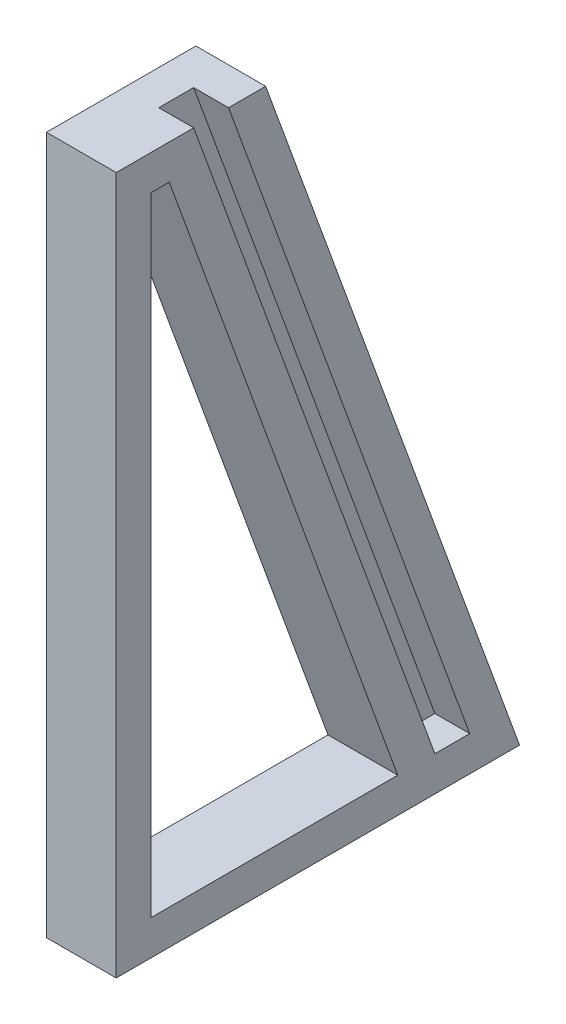
SolidWorks part; units mm, degrees
ref_plane "Front Plane" through (0, 0, 0) normal (0, 0, 1) x (1, 0, 0)
ref_plane "Top Plane" through (0, 0, 0) normal (0, 1, 0) x (1, 0, 0)
ref_plane "Right Plane" through (0, 0, 0) normal (1, 0, 0) x (0, 0, -1)
sketch "Sketch1" plane through (0, 0, 0) normal (1, 0, 0) x (0, 0, -1)
  line L1 (-50, 50) -> (50, 50)
  line L2 (-50, 50) -> (-50, -50)
  line L3 (-50, -50) -> (50, -50)
  line L4 (50, 50) -> (50, -50)
  line L5 (-50, 50) -> (50, -50) construction
  line L6 (-50, -50) -> (50, 50) construction
  point P0 (0, 0)
  dimension "D1" = 100
  dimension "D2" = 100
extrude "Boss-Extrude1" add sketch "Sketch1" along normal blind 10
sketch "Sketch2" plane through (0, 0, 0) normal (-1, 0, 0) x (0, 0, 1)
  line L0 (-50, -50) -> (-50, 50)
  line L1 (-50, 50) -> (50, 50)
  line L2 (50, 50) -> (50, -50)
  line L3 (50, -50) -> (-50, -50)
  line L4 (38.897, 50) -> (50, 50)
  line L5 (0, -50) -> (2.5, -50)
  line L6 (0, -50) -> (-2.5, -50)
  line L7 (36.397, 50) -> (38.897, 50)
  line L8 (36.397, 50) -> (33.897, 50)
  line L9 (33.897, 50) -> (-2.5, -50)
  line L10 (38.897, 50) -> (2.5, -50)
  line L11 (50, -50) -> (50, 50)
  line L12 (50, -50) -> (2.5, -50)
  line L13 (2.5, -50) -> (38.897, 50)
  line L14 (7.1985, -51.7101) -> (7.8209, -50)
  line L15 (45, 45) -> (45, -45)
  line L16 (45, -45) -> (9.6407, -45)
  line L17 (9.6407, -45) -> (42.3981, 45)
  line L18 (50, -45) -> (-45, -45) construction
  line L19 (7.1985, -51.7101) -> (43.5955, 48.2899) construction
  line L20 (45, 50) -> (45, -50) construction
  line L21 (42.3981, 45) -> (45, 45)
  line L22 (-45, 45) -> (50, 45) construction
  line L23 (-0.6801, -45) -> (4.3199, -45)
  line L24 (-45, -45) -> (-45, 45) construction
  line L25 (-50, 50) -> (33.897, 50)
  line L26 (-2.5, -50) -> (33.897, 50)
  line L27 (-50, 50) -> (-50, -50)
  line L28 (-2.5, -50) -> (-50, -50)
  line M16 (-50, 50) -> (-50, -50)
  line M17 (-50, -50) -> (50, -50)
  dimension "D1" = 5
  dimension "D2" = 2.5
  dimension "D3" = 2.5
  dimension "D4" = 70
extrude "Cut-Extrude1" cut sketch "Sketch2" against normal blind 10 contours L21 L17 L16 L15 region at (0, -12.9437, 33.1541)
sketch "Sketch3" plane through (0, -50, 0) normal (0, -1, 0) x (1, 0, 0)
  line L0 (10, 50) -> (10, -50)
sketch "Sketch4" plane through (0, -50, 0) normal (0, -1, 0) x (1, 0, 0)
  line L0 (10, 50) -> (10, -50)
  line L1 (10, -50) -> (0, -50)
  line L2 (0, -50) -> (0, 50)
  line L3 (0, 50) -> (10, 50)
  line L4 (0, 50) -> (0, 40)
  line L5 (0, 40) -> (10, 40)
  line L6 (10, 40) -> (10, 50)
  line L7 (10, -50) -> (10, -40)
  line L8 (10, -40) -> (0, -40)
  line L9 (0, -40) -> (0, -50)
  line L10 (10, 0) -> (0, 0)
  line L11 (10, 0) -> (10, 0.3209)
  line L12 (10, 0.3209) -> (0, 0.3209)
  line L13 (0, 0.3209) -> (0, 0)
  line L14 (0, 0.3209) -> (0, 10.3209)
  line L15 (0, 10.3209) -> (10, 10.3209)
  line L16 (10, 10.3209) -> (10, 0.3209)
  line L17 (10, 10.3209) -> (10, 5.3209)
  line L18 (10, 45) -> (5, 45)
  line L19 (5, 45) -> (5, 50)
  line L20 (8, 8.3209) -> (2, 8.3209)
  line L21 (8, 8.3209) -> (8, 2.3209)
  line L22 (8, 2.3209) -> (2, 2.3209)
  line L23 (2, 8.3209) -> (2, 2.3209)
  line L24 (8, 8.3209) -> (2, 2.3209) construction
  line L25 (8, 2.3209) -> (2, 8.3209) construction
  line L26 (8, -42) -> (2, -42)
  line L27 (8, 48) -> (2, 48)
  line L28 (8, 48) -> (8, 42)
  line L29 (8, 42) -> (2, 42)
  line L30 (2, 48) -> (2, 42)
  line L31 (8, 48) -> (2, 42) construction
  line L32 (8, 42) -> (2, 48) construction
  line L33 (2, -48) -> (2, -42)
  line L34 (8, -48) -> (2, -48)
  line L35 (8, -48) -> (8, -42)
  line L36 (5, 5.3209) -> (10, 5.3209)
  line L37 (5, 5.3209) -> (5, 0.3209)
  line L38 (5, -50) -> (5, -45)
  line L39 (5, -45) -> (10, -45)
  dimension "D1" = 6
  dimension "D2" = 6
  dimension "D3" = 6
  dimension "D4" = 6
extrude "Cut-Extrude3" cut sketch "Sketch4" against normal blind 4 contours L34 L35 L26 L33 | L20 L23 L22 L21 | L27 L30 L29 L28 L18 L19 | L28 L27 L19 L18 | L36 L37 L22 L21 | L39 L38 L34 L35 region at (4.5, -50, 44.5) region at (6.5, -50, 46.5) region at (4.5, -50, 5.8209) region at (6.5, -50, 3.8209) region at (4.5, -50, -44.5) region at (6.5, -50, -46.5)
sketch "Sketch6" plane through (10, 0, 0) normal (1, 0, 0) x (0, 0, -1)
  line L0 (-38.897, 50) -> (-33.897, 50)
  line L1 (-33.897, 50) -> (0.6801, -45)
  line L2 (0.6801, -45) -> (-4.3199, -45)
  line L3 (-4.3199, -45) -> (-38.897, 50)
extrude "Cut-Extrude5" cut sketch "Sketch2<4>" against normal blind 10 contours L9 L1 M16 M17 region at (0, 4.6167, -16.3106)
sketch "Sketch2<4>" plane through (0, 0, 0) normal (-1, 0, 0) x (0, 0, 1) same geometry as "Sketch2"
extrude "Cut-Extrude6" cut sketch "Sketch6" against normal blind 5
sketch "Sketch8" plane through (0, 0, 0) normal (-1, 0, 0) x (0, 0, 1)
  line L0 (33.897, 50) -> (-2.5, -50)
  line L1 (-2.5, -50) -> (-50, -50)
  line L2 (-50, -50) -> (-50, 50)
  line L3 (-50, 50) -> (33.897, 50)
  line L5 (26.7563, 45) -> (-6.001, -45)
  line L8 (26.7563, 45) -> (28.5761, 50)
  line L9 (-6.001, -45) -> (-7.8209, -50)
  line L11 (-45, 45) -> (26.7563, 45) construction
  line L12 (-6.001, -45) -> (-45, -45) construction
  line L13 (-45, -45) -> (-45, 45) construction
  line M15 (33.897, 50) -> (-2.5, -50)
  dimension "D2" = 180
  dimension "D3" = 180
  dimension "D1" = 5
extrude "Boss-Extrude2" add sketch "Sketch8" against normal blind 10 contours L5 L9 L1 L3 L8 M15 region at (0, 0, 13.0381)
sketch "Sketch9" plane through (0, 0, 0) normal (-1, 0, 0) x (0, 0, 1)
  line L0 (28.5761, 50) -> (33.897, 50)
  line L1 (33.897, 50) -> (38.897, 50)
